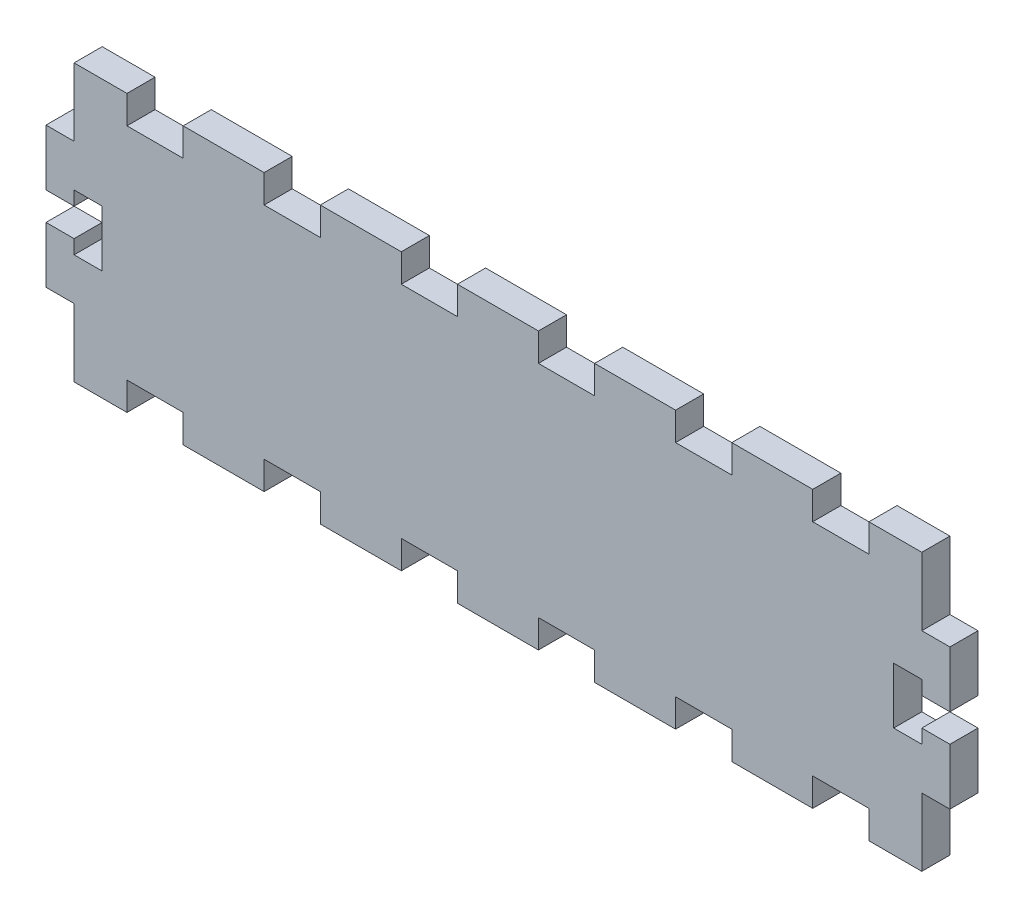
SolidWorks part; units mm, degrees
ref_plane "Front Plane" through (0, 0, 0) normal (0, 0, 1) x (1, 0, 0)
ref_plane "Top Plane" through (0, 0, 0) normal (0, 1, 0) x (1, 0, 0)
ref_plane "Right Plane" through (0, 0, 0) normal (1, 0, 0) x (0, 0, -1)
sketch "Sketch2" plane through (0, 0, 0) normal (0, 1, 0) x (1, 0, 0)
  line L0 (0, 0) -> (0, 6) construction
  dimension "D1" = 6
sketch "Sketch1" plane through (0, 0, 0) normal (0, 0, 1) x (1, 0, 0)
  line L1 (-96.5, -29.5) -> (96.5, -29.5)
  line L2 (-96.5, -29.5) -> (-96.5, 29.5)
  line L3 (-96.5, 29.5) -> (96.5, 29.5)
  line L4 (96.5, -29.5) -> (96.5, 29.5)
  line L5 (-96.5, -29.5) -> (96.5, 29.5) construction
  line L6 (-96.5, 29.5) -> (96.5, -29.5) construction
  point P0 (0, 0)
  dimension "D1" = 193
  dimension "D2" = 59
extrude "Boss-Extrude1" add sketch "Sketch1" against normal up to vertex (6 mm away) contours L2 L3 L4 L1 up to point (0, 0, -6)
sketch "Sketch3" plane through (0, 0, 0) normal (0, 0, 1) x (1, 0, 0)
  line L0 (-96.5, -29.5) -> (-96.5, 29.5) construction
  line L1 (-96.5, 15) -> (-90.5, 15) construction
  line L2 (-96.5, 15) -> (-96.5, 3) construction
  line L3 (-96.5, 3) -> (-90.5, 3) construction
  line L4 (-90.5, 15) -> (-90.5, 3) construction
  line L5 (-84.5, -6) -> (-84.5, -29.5) construction
  line L6 (-90.5, 3) -> (-96.5, 3)
  line L7 (-90.5, 3) -> (-90.5, -3)
  line L8 (-90.5, -3) -> (-96.5, -3)
  line L9 (-96.5, 3) -> (-96.5, -3)
  line L10 (-96.5, -3) -> (-90.5, -3) construction
  line L11 (-96.5, -3) -> (-96.5, -15) construction
  line L12 (-96.5, -15) -> (-90.5, -15) construction
  line L13 (-90.5, -3) -> (-90.5, -15) construction
  line L14 (-90.5, 15) -> (-96.5, 15)
  line L15 (-90.5, 15) -> (-90.5, 29.5)
  line L16 (-90.5, 29.5) -> (-96.5, 29.5)
  line L17 (-96.5, 15) -> (-96.5, 29.5)
  line L18 (-90.5, -15) -> (-96.5, -15)
  line L19 (-90.5, -15) -> (-90.5, -29.5)
  line L20 (-90.5, -29.5) -> (-96.5, -29.5)
  line L21 (-96.5, -15) -> (-96.5, -29.5)
  line L22 (-90.5, 6) -> (-84.5, 6)
  line L23 (-90.5, 6) -> (-90.5, -6)
  line L24 (-90.5, -6) -> (-84.5, -6)
  line L25 (-84.5, 6) -> (-84.5, -6)
  line L26 (-96.5, -29.5) -> (96.5, -29.5) construction
  line L27 (-84.5, 6) -> (-84.5, 29.5) construction
  line L28 (-96.5, 29.5) -> (96.5, 29.5) construction
  line L29 (0, 0) -> (0, -29.5) construction
  line L30 (-67.2143, -23.5) -> (-49.9286, -23.5) construction
  line L31 (-37.9286, -23.5) -> (-20.6429, -23.5) construction
  line L32 (-37.9286, -23.5) -> (-49.9286, -23.5)
  line L33 (-37.9286, -23.5) -> (-37.9286, -29.5)
  line L34 (-37.9286, -29.5) -> (-49.9286, -29.5)
  line L35 (-49.9286, -23.5) -> (-49.9286, -29.5)
  line L36 (-8.6429, -23.5) -> (-20.6429, -23.5)
  line L37 (-8.6429, -23.5) -> (-8.6429, -29.5)
  line L38 (-8.6429, -29.5) -> (-20.6429, -29.5)
  line L39 (-20.6429, -23.5) -> (-20.6429, -29.5)
  line L40 (-67.2143, -23.5) -> (-79.2143, -23.5)
  line L41 (-67.2143, -23.5) -> (-67.2143, -29.5)
  line L42 (-67.2143, -29.5) -> (-79.2143, -29.5)
  line L43 (-79.2143, -23.5) -> (-79.2143, -29.5)
  line L44 (-8.6429, -23.5) -> (8.6429, -23.5) construction
  line L45 (-79.2143, -23.5) -> (-96.5, -23.5) construction
  line L46 (-96.5, -23.5) -> (-96.5, -29.5) construction
  point P32 (0, -23.5)
  dimension "D1" = 6
  dimension "D2" = 12
  dimension "D3" = 6
  dimension "D4" = 12
extrude "Cut-Extrude1" cut sketch "Sketch3" against normal through all contours L25 L22 L23 L7 L24 | L6 L9 L8 L7 | L17 L14 L15 L16 | L18 L21 L20 L19 region at (-93.5, 0, 0) region at (-87.5, 0, 0) region at (-93.5, 22.25, 0) region at (-93.5, -22.25, 0)
extrude "Cut-Extrude2" cut sketch "Sketch3<3>" against normal through all contours L40 L43 L42 L41 | L32 L35 L34 L33 | L36 L39 L38 L37 region at (-43.9286, -26.5, 0) region at (-14.6429, -26.5, 0) region at (-73.2143, -26.5, 0)
sketch "Sketch3<3>" plane through (0, 0, 0) normal (0, 0, 1) x (1, 0, 0) same geometry as "Sketch3"
mirror "Mirror1" about plane through (0, 0, 0) normal (1, 0, 0) of "Cut-Extrude2" second plane through (0, 0, 0) second plane normal (0, 1, 0)
mirror "Mirror2" about plane through (0, 0, 0) normal (1, 0, 0) of "Cut-Extrude1"
equation "\"t_wood\"= 6' Thickness of the wood"
equation "\"t_glass\"= 2.5'Thickness of glass panels"
equation "\"w_glass\"= 181"
equation "\"h_glass\"= 151"
equation "\"h_food_internal\" = 60"
equation "\"entry_height\"= 20"
equation "\"entry diameter\"= 8"
equation "\"glass_bottom_overlap\"= 8"
equation "\"default_finger_size\"= 12"
equation "\"brood_depth\"= 42"
equation "\"outer_box_depth\" = \"brood_depth\" + ( 2 * \"t_glass\" ) + ( 2 * \"t_wood\" )"
equation "\"outer_box_width\"= \"w_glass\" + ( 2 * \"t_wood\" )"
equation "\"food_top_clearance\"= 10"
equation "\"outer_box_height\"= \"t_wood\" + \"h_glass\" + \"t_wood\" + \"h_food_internal\" + \"food_top_clearance\" + \"t_wood\""
equation "\"food_internal_depth\"= \"brood_depth\" + \"t_glass\" + \"t_glass\" - \"t_wood\" - \"t_wood\""
equation "\"food_channel_clearance_width\"= 14"
equation "\"bar_top_play\"= 0.5"
equation "\"bar_entry_angle\"= 10"
equation "\"bar_width\"= 20"
equation "\"entry_disk_play\"= 0.3"
equation "\"D1@Sketch2\"=\"t_wood\""
equation "\"D1@Sketch1\"=\"outer_box_width\""
equation "\"D2@Sketch1\"=\"outer_box_depth\""
equation "\"D1@Sketch3\"=\"t_wood\""
equation "\"D2@Sketch3\"=\"default_finger_size\""
equation "\"D3@Sketch3\"=\"t_wood\""
equation "\"D4@Sketch3\"=\"default_finger_size\""
